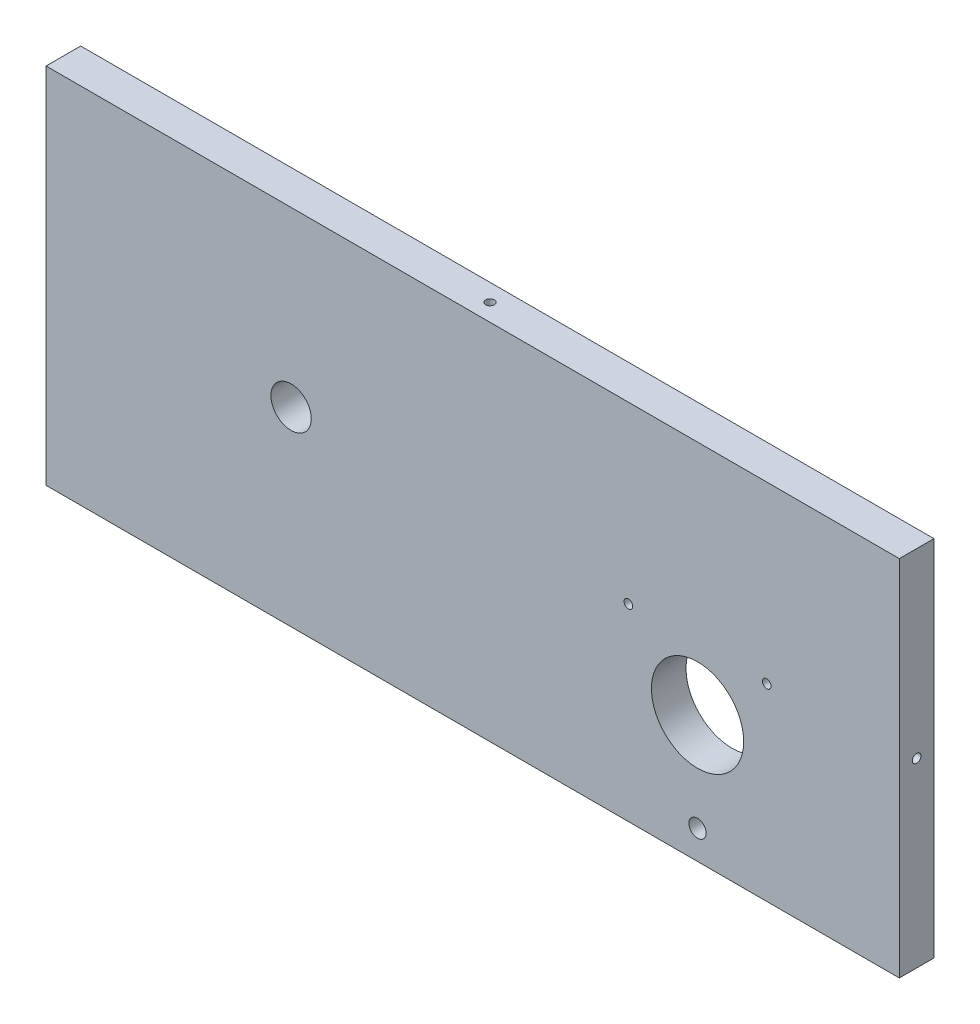
SolidWorks part; units mm, degrees
ref_plane "Front Plane" through (0, 0, 0) normal (0, 0, 1) x (1, 0, 0)
ref_plane "Top Plane" through (0, 0, 0) normal (0, 1, 0) x (1, 0, 0)
ref_plane "Right Plane" through (0, 0, 0) normal (1, 0, 0) x (0, 0, -1)
sketch "Sketch1" plane through (0, 0, 0) normal (0, 0, 1) x (1, 0, 0)
  line L0 (29.9224, 29.6979) -> (179.9891, 29.6979) construction
  line L1 (-132.5143, 90.2979) -> (163.4857, 90.2979)
  line L2 (-132.5143, 90.2979) -> (-132.5143, -35.7021)
  line L3 (-132.5143, -35.7021) -> (163.4857, -35.7021)
  line L4 (163.4857, 90.2979) -> (163.4857, -35.7021)
  line L5 (93.4857, 8.2979) -> (93.4857, -35.7021) construction
  line L6 (93.4857, -35.7021) -> (93.4857, 8.2979) construction
  circle A0 centre (93.4857, 8.2979) radius 16
  circle A1 centre (-47.5143, 30.2979) radius 7
  circle A2 centre (69.4857, 29.6979) radius 1.5
  circle A3 centre (117.4857, 29.6979) radius 1.5
  circle A4 centre (93.4857, -25.7021) radius 3
  dimension "D3" = 32
  dimension "D4" = 14
  dimension "D7" = 3
  dimension "D8" = 3
  dimension "D12" = 6
  dimension "D1" = 296
  dimension "D2" = 126
  dimension "D5" = 85
  dimension "D6" = 66
  dimension "D9" = 48
  dimension "D10" = 24
  dimension "D11" = 65.4
  dimension "D13" = 44
  dimension "D14" = 70
  dimension "D15" = 10
extrude "Boss-Extrude1" add sketch "Sketch1" along normal blind 12
sketch "Sketch2" plane through (0, 0, 0) normal (0, 1, 0) x (1, 0, 0)
  line L0 (-132.5143, -6) -> (163.4857, -6) construction
  line L1 (-132.5143, -12) -> (-132.5143, 0) construction
  line L2 (163.4857, -12) -> (163.4857, 0) construction
  circle A0 centre (15.4857, -6) radius 1.5
  dimension "D1" = 3
extrude "Cut-Extrude1" cut sketch "Sketch2" against normal blind 20 from surface starting at face at (15.4857, 90.2979, 6)
sketch "Sketch3" plane through (0, 0, 0) normal (1, 0, 0) x (0, 0, -1)
  line L0 (-12, 27.2979) -> (0, 27.2979) construction
  line L1 (-12, -35.7021) -> (-12, 90.2979) construction
  line L2 (0, -35.7021) -> (0, 90.2979) construction
  line L3 (-6, 90.2979) -> (-6, -35.7021) construction
  line L4 (-12, 90.2979) -> (0, 90.2979) construction
  line L5 (-12, -35.7021) -> (0, -35.7021) construction
  circle A0 centre (-6, 27.2979) radius 1.5
  dimension "D1" = 3
extrude "Cut-Extrude3" cut sketch "Sketch3" against normal blind 20 from surface starting at face at (163.4857, 27.2979, 6)
extrude "Cut-Extrude4" cut sketch "Sketch3<2>" along normal blind 20 from surface starting at face at (-132.5143, 27.2979, 6)
sketch "Sketch3<2>" plane through (0, 0, 0) normal (1, 0, 0) x (0, 0, -1) same geometry as "Sketch3"
sketch "Sketch4" plane through (0, 0, 0) normal (0, 0, 1) x (1, 0, 0)
  circle A0 centre (117.4857, 29.6979) radius 3
  circle A1 centre (69.4857, 29.6979) radius 3
  dimension "D1" = 6
  dimension "D2" = 6
extrude "Cut-Extrude5" cut sketch "Sketch4" along normal blind 3 draft 45 from surface starting at face at (15.4857, 27.2979, 0)
